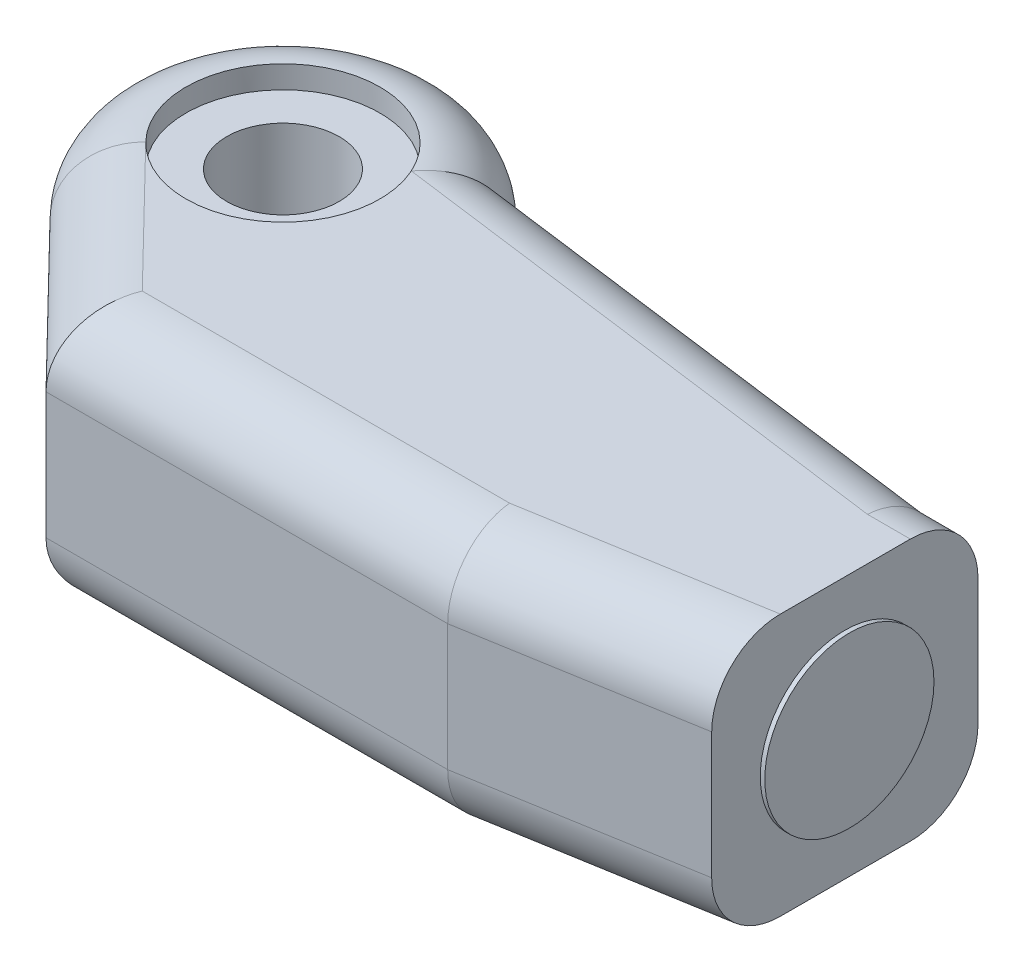
SolidWorks part; units mm, degrees
ref_plane "Front Plane" through (0, 0, 0) normal (0, 0, 1) x (1, 0, 0)
ref_plane "Top Plane" through (0, 0, 0) normal (0, 1, 0) x (1, 0, 0)
ref_plane "Right Plane" through (0, 0, 0) normal (1, 0, 0) x (0, 0, -1)
sketch "Sketch1" plane through (0, 0, 0) normal (0, 1, 0) x (1, 0, 0)
  line L0 (0, 0) -> (291, 0) construction
  line L1 (291, 0) -> (291, 17)
  line L2 (291, 17) -> (274, 17)
  line L3 (274, 17) -> (57, 45.607)
  line L4 (291, 0) -> (291, -101)
  line L5 (291, -101) -> (191, -118)
  line L6 (191, -118) -> (13, -118)
  line L7 (-52.3049, -50.9234) -> (13, -118)
  arc A0 (57, 45.607) -> (-52.3049, -50.9234) centre (0, 0) ccw
  dimension "D1" = 291
  dimension "D2" = 146
  dimension "D3" = 17
  dimension "D4" = 17
  dimension "D5" = 217
  dimension "D6" = 101
  dimension "D7" = 100
  dimension "D8" = 118
  dimension "D9" = 178
extrude "Boss-Extrude1" add sketch "Sketch1" along normal mid plane 116
sketch "Sketch2" plane through (291, 0, 0) normal (1, 0, 0) x (0, 0, -1)
  circle A0 centre (-42, 0) radius 37.5
  dimension "D1" = 75
extrude "Boss-Extrude2" add sketch "Sketch2" along normal blind 2
fillet "Fillet1" radius 30 10 edges at (241, 58, 109.5) (102, 58, 118) (-19.6525, 58, 84.4617) (165.5, 58, -31.3035) (-48.3223, 58, -54.7171) (165.5, -58, -31.3035) (-48.3223, -58, -54.7171) (-19.6525, -58, 84.4617) (102, -58, 118) (241, -58, 109.5)
fillet "Fillet2" radius 30 2 edges at (167.7323, 58, -17) (167.7323, -58, -17)
sketch "Sketch3" plane through (0, 58, 0) normal (0, 1, 0) x (1, 0, 0)
  circle A0 centre (0, 0) radius 43
extrude "Cut-Extrude1" cut sketch "Sketch3" against normal blind 10
mirror "Mirror1" about plane through (0, 0, 0) normal (0, 1, 0) of "Cut-Extrude1"
sketch "Sketch4" plane through (0, -48, 0) normal (0, -1, 0) x (-1, 0, 0)
  circle A0 centre (0, 0) radius 24.9233
extrude "Cut-Extrude2" cut sketch "Sketch4" against normal blind 500
